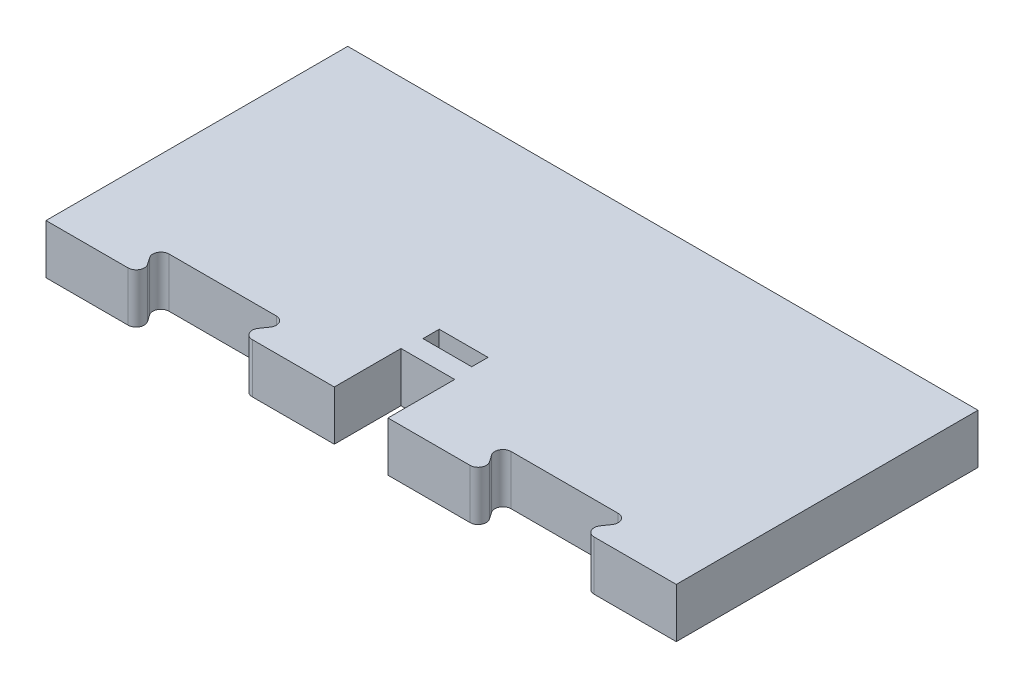
SolidWorks part; units mm, degrees
ref_plane "Front Plane" through (0, 0, 0) normal (0, 0, 1) x (1, 0, 0)
ref_plane "Top Plane" through (0, 0, 0) normal (0, 1, 0) x (1, 0, 0)
ref_plane "Right Plane" through (0, 0, 0) normal (1, 0, 0) x (0, 0, -1)
sketch "Sketch1" plane through (0, 0, 0) normal (0, 1, 0) x (1, 0, 0)
  line L0 (0, 0) -> (38.75, 0)
  line L1 (0, 0) -> (0, 8.3)
  line L2 (38.75, 0) -> (38.75, 8.3)
  line L3 (0, 8.3) -> (38.75, 8.3)
  dimension "D1" = 8.3
  dimension "D2" = 38.75
extrude "Boss-Extrude1" add sketch "Sketch1" along normal blind 3.05
sketch "Sketch3" plane through (0, 3.05, 0) normal (0, 1, 0) x (1, 0, 0)
  line L0 (19.375, 8.3) -> (19.375, 6.3)
  line L1 (38.75, 8.3) -> (0, 8.3) construction
  line L2 (20.875, 6.3) -> (17.875, 6.3)
  line L3 (17.875, 6.3) -> (17.875, 5.3)
  line L4 (17.875, 5.3) -> (20.875, 5.3)
  line L5 (20.875, 5.3) -> (20.875, 6.3)
  line L6 (19.375, 5.3) -> (19.375, 4.1)
  line L7 (21.025, 4.1) -> (17.725, 4.1)
  line L8 (17.725, 4.1) -> (17.725, 0)
  line L9 (0, 0) -> (38.75, 0) construction
  line L10 (17.725, 0) -> (21.025, 0)
  line L11 (21.025, 0) -> (21.025, 4.1)
  point P7 (19.375, 6.3)
  point P14 (19.375, 4.1)
  line M9 (0, 0) -> (38.75, 0)
  dimension "D1" = 2
  dimension "D2" = 1
  dimension "D3" = 1.2
  dimension "D4" = 3.3
  dimension "D5" = 3
extrude "Cut-Extrude2" cut sketch "Sketch3" against normal through all contours L11 L7 L8 M9 | L4 L5 L2 L3 region at (19.375, 3.05, -5.8) region at (19.375, 3.05, -2.05)
sketch "Sketch2" plane through (0, 3.05, 0) normal (0, 1, 0) x (1, 0, 0)
  line L0 (0, 0) -> (0, 2)
  line L1 (0, 8.3) -> (0, 0) construction
  line L2 (0, 2) -> (38.75, 2) construction
  line L3 (38.75, 0) -> (38.75, 8.3) construction
  line L4 (0, 0) -> (6, 0)
  line L5 (0, 0) -> (17.725, 0) construction
  line L6 (6, 0) -> (4.6125, 2)
  line L7 (4.6125, 2) -> (13.1125, 2)
  line L8 (13.1125, 2) -> (11.725, 0)
  line L9 (11.725, 0) -> (17.725, 0)
  line L10 (27.025, 0) -> (25.6375, 2)
  line L11 (25.6375, 2) -> (34.1375, 2)
  line L12 (34.1375, 2) -> (32.75, 0)
  line L13 (32.75, 0) -> (38.75, 0)
  line L14 (6, 0) -> (11.725, 0)
  line L15 (27.025, 0) -> (32.75, 0)
  line L16 (0, 2) -> (4.6125, 2)
  line L17 (34.1375, 2) -> (38.75, 2)
  line L18 (38.75, 2) -> (38.75, 0)
  line L19 (21.025, 0) -> (27.025, 0)
  line L20 (13.1125, 2) -> (17.725, 2)
  line L21 (17.725, 4.1) -> (17.725, 0) construction
  line L22 (17.725, 2) -> (17.725, 0)
  line L23 (21.025, 0) -> (21.025, 2)
  line L24 (21.025, 0) -> (21.025, 4.1) construction
  line L25 (21.025, 2) -> (25.6375, 2)
  line M9 (0, 0) -> (17.725, 0)
  dimension "D1" = 2
  dimension "D2" = 6
  dimension "D4" = 8.5
extrude "Cut-Extrude1" cut sketch "Sketch2" against normal through all contours L8 L6 M9 | L12 L10 M9 region at (8.8625, 3.05, -1.065) region at (29.8875, 3.05, -1.065)
fillet "Fillet1" radius 0.5 8 edges at (32.75, 1.525, 0) (27.025, 1.525, 0) (11.725, 1.525, 0) (6, 1.525, 0) (25.6375, 1.525, -2) (34.1375, 1.525, -2) (13.1125, 1.525, -2) (4.6125, 1.525, -2)
sketch "Sketch4" plane through (0, 0, -8.3) normal (0, 0, -1) x (-1, 0, 0)
  line L0 (-38.75, 3.05) -> (0, 3.05)
  line L1 (-38.75, 3.05) -> (-38.75, 0)
  line L2 (0, 3.05) -> (0, 0)
  line L3 (-38.75, 0) -> (0, 0)
extrude "Boss-Extrude2" add sketch "Sketch4" along normal blind 10.25
